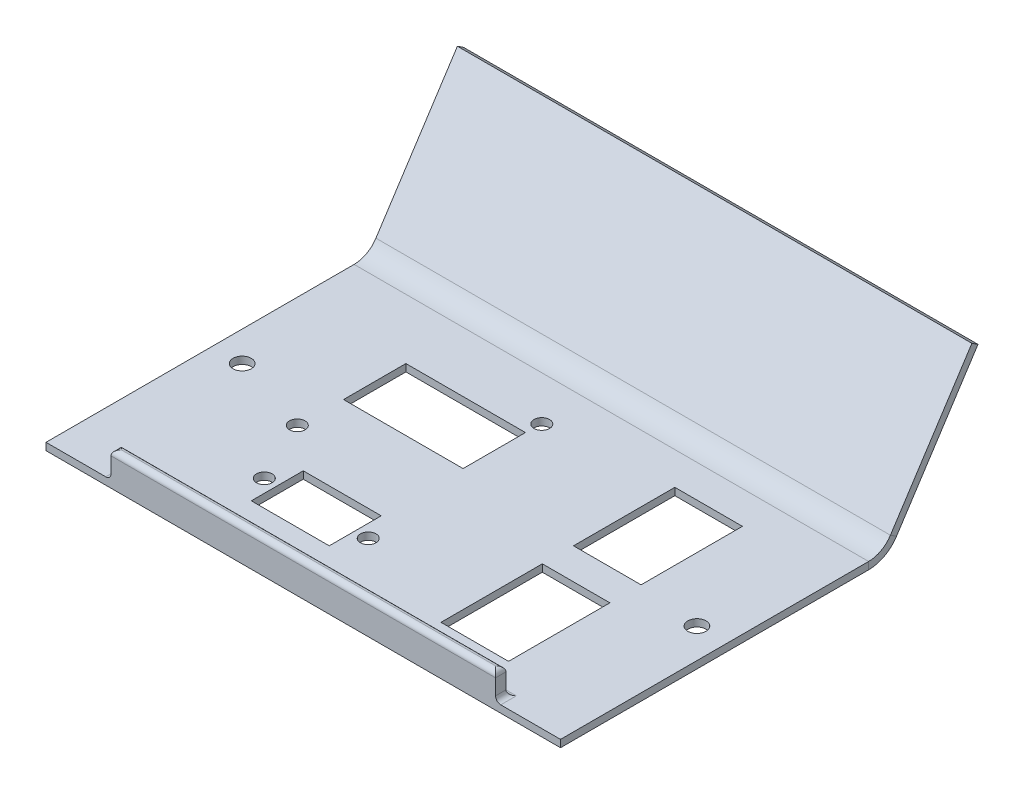
SolidWorks part; units mm, degrees
note: The reader was unsure of these and kept them because the rebuilt part matched: bend radius of "Pli de base1".
material "ABS"
ref_plane "Front" through (0, 0, 0) normal (0, 0, 1) x (1, 0, 0)
ref_plane "Top" through (0, 0, 0) normal (0, 1, 0) x (1, 0, 0)
ref_plane "Right" through (0, 0, 0) normal (1, 0, 0) x (0, 0, -1)
sketch "Esquisse1" plane through (0, 0, 0) normal (1, 0, 0) x (0, 0, -1)
  line L0 (0, 0) -> (62, 0)
  line L1 (62, 0) -> (79.1561, 26.4181)
  dimension "D1" = 62
  dimension "D2" = 31.5
  dimension "D3" = 57
base flange "Tôle de base pliée1" sketch "Esquisse1" end condition mid plane depth 99 reverse direction no thickness 1.4 reverse thickness direction no bend radius 5
bend "Pli de base1" bend radius 5 bend angle 57 parameters "D5"=1
sketch "Esquisse6" plane through (0, -1.4, 0) normal (0, -1, 0) x (1, 0, 0)
  line L1 (0, -50) -> (0, 50) construction
  line L2 (49.5, 0) -> (-49.5, 0) construction
  circle A0 centre (-43.75, -32) radius 1.75
  circle A2 centre (43.75, -32) radius 1.75
  dimension "D1" = 87.5
  dimension "D2" = 3.5
  dimension "D3" = 32
extrude "Enlèv. mat.-Extru.1" cut sketch "Esquisse6" against normal through all normal cut yes
sketch "Esquisse7" plane through (0, -1.4, 0) normal (0, -1, 0) x (1, 0, 0)
  line L5 (18.5, -8) -> (31.5, -8)
  line L6 (18.5, -8) -> (18.5, -27.5)
  line L7 (18.5, -27.5) -> (31.5, -27.5)
  line L8 (31.5, -8) -> (31.5, -27.5)
  line L13 (49.5, 0) -> (-49.5, 0) construction
  line L14 (-16.5, -35.75) -> (-16.5, -38.875) construction
  line L15 (-28, -35.75) -> (-5, -35.75)
  line L16 (-28, -35.75) -> (-28, -47.75)
  line L17 (-28, -47.75) -> (-5, -47.75)
  line L18 (-5, -35.75) -> (-5, -47.75)
  line L19 (-16.5, -38.875) -> (-28, -38.875) construction
  line L20 (49.5, -30.5) -> (31.5, -30.5) construction
  line L21 (-49.5, 0) -> (-49.5, -59.2852) construction
  line L22 (18.5, -33.5) -> (31.5, -33.5)
  line L23 (31.5, -53) -> (31.5, -33.5)
  line L24 (18.5, -53) -> (31.5, -53)
  line L25 (18.5, -53) -> (18.5, -33.5)
  line L26 (49.5, 0) -> (49.5, -59.2852) construction
  line L27 (-12.5, -20) -> (-12.5, -10) construction
  line L28 (-2.85, -52.75) -> (-30.15, -52.75) construction
  line L29 (-2.85, -52.75) -> (-2.85, -25) construction
  line L30 (-2.85, -25) -> (-30.15, -25) construction
  line L31 (-30.15, -52.75) -> (-30.15, -25) construction
  line L32 (-5, -20) -> (-20, -20)
  line L33 (-5, -20) -> (-5, -10)
  line L34 (-5, -10) -> (-20, -10)
  line L35 (-20, -20) -> (-20, -10)
  circle A0 centre (-28.15, -27) radius 1.5
  circle A1 centre (-28.15, -50.75) radius 1.5 construction
  circle A2 centre (-4.85, -50.75) radius 1.5
  circle A3 centre (-4.85, -27) radius 1.5 construction
  circle A4 centre (-2.5, -15) radius 1.5
  circle A5 centre (-22.5, -15) radius 1.5
  point P32 (-16.5, -52.75)
  point P33 (-30.15, -38.875)
  point P34 (-5, -41.75)
  point P49 (-12.5, -15)
  dimension "D5" = 12
  dimension "D7" = 2
  dimension "D8" = 2
  dimension "D10" = 3
  dimension "D15" = 20
  dimension "D19" = 3
  dimension "D20" = 15
  dimension "D1" = 13
  dimension "D2" = 19.5
  dimension "D3" = 18
  dimension "D4" = 8
  dimension "D6" = 23
  dimension "D9" = 27.3
  dimension "D11" = 6
  dimension "D12" = 33
  dimension "D13" = 27.75
  dimension "D14" = 25
  dimension "D16" = 15
  dimension "D17" = 11
  dimension "D18" = 10
extrude "Enlèv. mat.-Extru.2" cut sketch "Esquisse7" against normal blind 1.4 normal cut yes
sketch "Esquisse10" plane through (0, -1.4, 0) normal (0, -1, 0) x (1, 0, 0)
  line L4 (-49.5, 0) -> (-49.5, -59.2852)
  line L5 (-49.5, -59.2852) -> (49.5, -59.2852)
  line L6 (49.5, -59.2852) -> (49.5, 0)
  line L7 (49.5, 0) -> (-49.5, 0)
  line L8 (-49.5, 0) -> (-49.5, -59.2852)
  line L9 (-49.5, -59.2852) -> (49.5, -59.2852)
  line L10 (49.5, -59.2852) -> (49.5, 0)
  line L11 (49.5, 0) -> (-49.5, 0)
  dimension "D1" = 0
extrude "Boss.-Extru.1" [suppressed] add sketch "Esquisse10" against normal blind 0.2
sketch "Esquisse11" plane through (0, 0, 0) normal (0, 1, 0) x (1, 0, 0)
  line L1 (-37, 2) -> (37, 2)
  line L2 (-37, 2) -> (-37, 0)
  line L3 (-37, 0) -> (37, 0)
  line L4 (37, 2) -> (37, 0)
  dimension "D1" = 2
  dimension "D2" = 74
extrude "Boss.-Extru.2" add sketch "Esquisse11" along normal blind 5
fillet "Congé1" radius 1 7 edges at (37, 0, -1) (0, 0, -2) (-37, 0, -1) (0, 5, -2) (37, 5, -1) (0, 5, 0) (-37, 5, -1)
sketch "Lignes de pliage1" [suppressed] plane through (0, 0, 0) normal (0, 1, 0) x (1, 0, 0)
sketch "Cube de visualisation1" [suppressed] plane through (0, 0, 0) normal (0, 1, 0) x (1, 0, 0)
sheet metal parameters "Tôlerie1" thickness 1.4 parameters "D1"=5
flat pattern "Etat déplié1" [suppressed]
sketch "Lignes de pliage2" plane through (0, 0, 0) normal (0, 1, 0) x (1, 0, 0)
  line L0 (-45, 66.16) -> (45, 66.16) construction
  line L1 (-45, 66.16) -> (45, 66.16) construction
sketch3d "Cube de visualisation2" [suppressed]
  line L0 (-90, 111.5678, 0) -> (-90, 0, 0) construction
  line L1 (0, 111.5678, 0) -> (0, 0, 0) construction
  line L2 (-90, 111.5678, 0) -> (0, 111.5678, 0) construction
  line L3 (-90, 0, 0) -> (0, 0, 0) construction
bend of the flat pattern "Dépliage-<Pli de base1>1"
sheet metal parameters "Tôlerie2" thickness 1.4 parameters "D1"=5
flat pattern "Etat déplié1"
sketch "Lignes de pliage2" plane through (0, 0, 0) normal (0, 1, 0) x (1, 0, 0)
  line L0 (-49.5, 62.1205) -> (49.5, 62.1205) construction
  line L1 (-49.5, 62.1205) -> (49.5, 62.1205) construction
sketch3d "Cube de visualisation2" [suppressed]
  line L0 (0, 0, 0) -> (-99, 0, 0) construction
  line L1 (0, 93.741, 0) -> (-99, 93.741, 0) construction
  line L2 (0, 0, 0) -> (0, 93.741, 0) construction
  line L3 (-99, 0, 0) -> (-99, 93.741, 0) construction
bend of the flat pattern "Dépliage-<Pli de base1>1"
sheet metal parameters "Tôlerie3" thickness 1.4 parameters "D1"=5
flat pattern "Etat déplié1"
sketch "Lignes de pliage2" plane through (0, 0, 0) normal (0, 1, 0) x (1, 0, 0)
  line L0 (-49.5, 62.1205) -> (49.5, 62.1205) construction
  line L1 (-49.5, 62.1205) -> (49.5, 62.1205) construction
sketch3d "Cube de visualisation2" [suppressed]
  line L0 (0, 0, 0) -> (-99, 0, 0) construction
  line L1 (0, 93.741, 0) -> (-99, 93.741, 0) construction
  line L2 (0, 0, 0) -> (0, 93.741, 0) construction
  line L3 (-99, 0, 0) -> (-99, 93.741, 0) construction
bend of the flat pattern "Dépliage-<Pli de base1>1"
sheet metal parameters "Tôlerie6" thickness 1.4 parameters "D1"=5
flat pattern "Etat déplié1"
sketch "Lignes de pliage2" plane through (0, 0, 0) normal (0, 1, 0) x (1, 0, 0)
  line L0 (-49.5, 62.1205) -> (49.5, 62.1205) construction
  line L1 (-49.5, 62.1205) -> (49.5, 62.1205) construction
sketch3d "Cube de visualisation2" [suppressed]
  line L0 (0, 0, -1.4) -> (-99, 0, -1.4) construction
  line L1 (0, 93.741, -1.4) -> (-99, 93.741, -1.4) construction
  line L2 (0, 0, -1.4) -> (0, 93.741, -1.4) construction
  line L3 (-99, 0, -1.4) -> (-99, 93.741, -1.4) construction
bend of the flat pattern "Dépliage-<Pli de base1>1"
